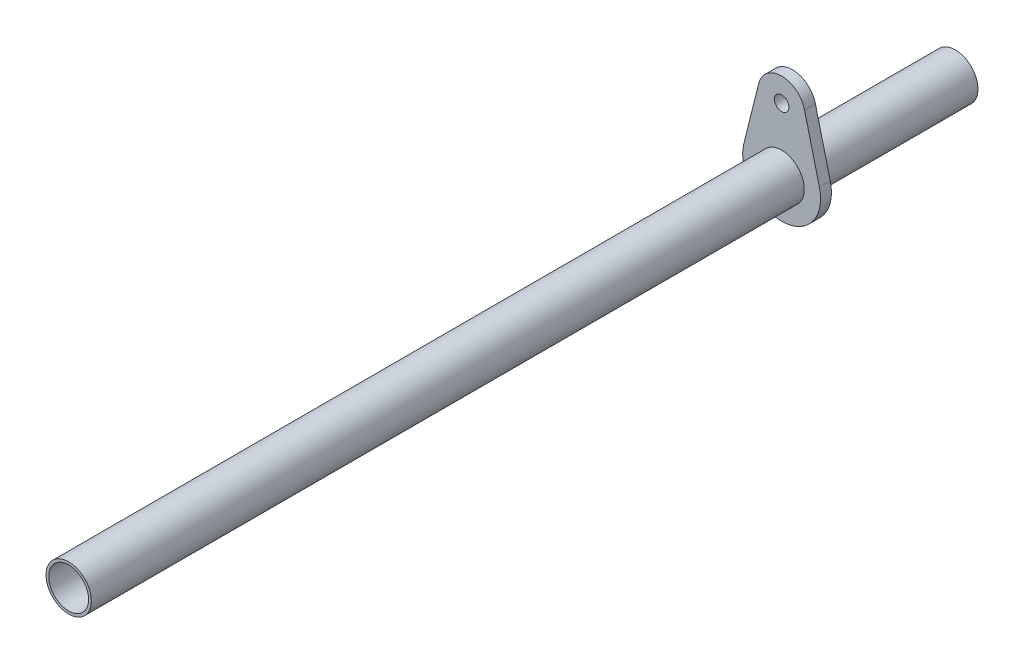
SolidWorks part; units mm, degrees
material "Aluminium 6060 T6"
ref_plane "Front Plane" through (0, 0, 0) normal (0, 0, 1) x (1, 0, 0)
ref_plane "Top Plane" through (0, 0, 0) normal (0, 1, 0) x (1, 0, 0)
ref_plane "Right Plane" through (0, 0, 0) normal (1, 0, 0) x (0, 0, -1)
sketch "Sketch1" plane through (0, 0, 0) normal (0, 0, 1) x (1, 0, 0)
  line L0 (-20.8806, 5.2275) -> (-12.6351, 38.1632)
  line L1 (12.6351, 38.1632) -> (20.8806, 5.2275)
  line L2 (0, 105.6938) -> (0, -51.0495) construction
  circle A0 centre (0, 0) radius 12.525
  arc A1 (-12.6351, 38.1632) -> (12.6351, 38.1632) centre (0, 35) cw
  arc A2 (20.8806, 5.2275) -> (-20.8806, 5.2275) centre (0, 0) cw
  circle A3 centre (0, 35) radius 4.025
  dimension "D1" = 25.05
  dimension "D5" = 8.05
  dimension "D2" = 9
  dimension "D3" = 35
  dimension "D4" = 9
extrude "Extrude-Thin1" add sketch "Sketch1" along normal blind 490 thin contours A0 thin type one direction reverse wall 1.5
extrude "Boss-Extrude2" add sketch "Sketch1<4>" along normal blind 6 from offset 90
sketch "Sketch1<4>" plane through (0, 0, 0) normal (0, 0, 1) x (1, 0, 0) same geometry as "Sketch1"
equation "\"D4@Sketch1\"=\"D2@Sketch1\""
